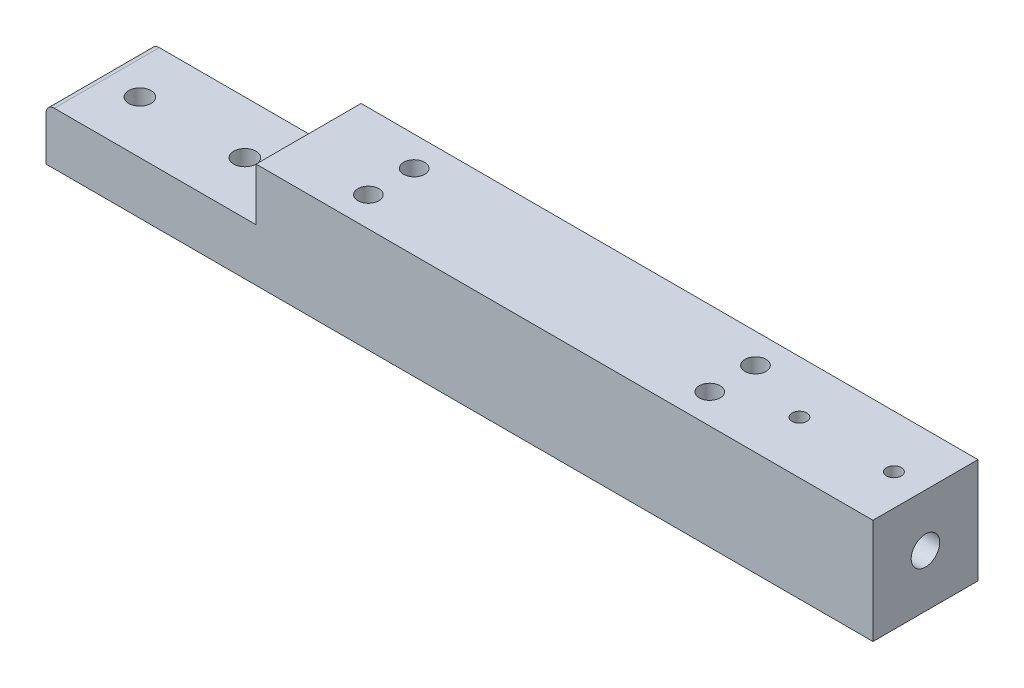
SolidWorks part; units mm, degrees
material "AISI 1020"
ref_plane "Front" through (0, 0, 0) normal (0, 0, 1) x (1, 0, 0)
ref_plane "Top" through (0, 0, 0) normal (0, 1, 0) x (1, 0, 0)
ref_plane "Right" through (0, 0, 0) normal (1, 0, 0) x (0, 0, -1)
sketch "Sketch1" plane through (0, 0, 0) normal (0, 0, 1) x (1, 0, 0)
  line L1 (0, 6.35) -> (100, 6.35)
  line L2 (0, 6.35) -> (0, -6.35)
  line L3 (0, -6.35) -> (100, -6.35)
  line L4 (100, 6.35) -> (100, -6.35)
  point P4 (0, 0)
  dimension "D1" = 12.7
  dimension "D2" = 100
extrude "Boss-Extrude1" add sketch "Sketch1" along normal mid plane 12.7
sketch "Sketch2" plane through (0, 0, 6.35) normal (0, 0, 1) x (1, 0, 0)
  line L1 (0, 6.35) -> (25.4, 6.35)
  line L2 (0, 6.35) -> (0, 0)
  line L3 (0, 0) -> (25.4, 0)
  line L4 (25.4, 6.35) -> (25.4, 0)
  dimension "D1" = 25.4
  dimension "D2" = 6.35
extrude "Cut-Extrude1" cut sketch "Sketch2" against normal through all
hole_wizard "#6-32 Tapped Hole1" positions "Sketch4" profile "Sketch5" tap size "#6-32" standard "Ansi Inch" end condition through all
sketch "Sketch4" plane through (0, 0, 0) normal (0, 1, 0) x (-1, 0, 0)
  line L0 (50, 0) -> (-50, 0) construction
  point P0 (-17.7, 0)
  point P1 (-5, 0)
sketch "Sketch5" plane through (17.7, 0, 0) normal (1, 0, 0) x (0, 0, 1)
  line L0 (0, 0) -> (0, 6.35)
  line L1 (0, 6.35) -> (1.3525, 6.35)
  line L2 (1.3525, 6.35) -> (1.3525, 0)
  line L5 (1.3525, 0) -> (0, 0)
  line L11 (0, -6.35) -> (0, 107.95) construction
  dimension "Thru Tap Drill Dia." = 2.7051
  dimension "Thru Tap Drill Depth" = 6.35
cosmetic thread "Hole Thread1" parameters "D2"=3.5052
cosmetic thread "Hole Thread2" parameters "D2"=3.5052
sketch "Sketch8" plane through (0, -6.35, 0) normal (0, 1, 0) x (1, 0, 0)
  line L0 (31.14, 4.0386) -> (66.14, 4.0386)
  line L1 (31.14, 1.4986) -> (66.14, 1.4986)
  line L2 (30.5743, 0) -> (90.4845, 0) construction
  line L3 (71.88, 12.488) -> (71.88, -9.4269) construction
  line L4 (100, -6.35) -> (100, 6.35) construction
  line L5 (25.4, 2.7686) -> (71.88, 2.7686) construction
  line L6 (25.4, 6.35) -> (25.4, -6.35) construction
  line L7 (31.14, 4.0386) -> (66.14, 1.4986) construction
  arc A0 (31.14, 1.4986) -> (31.14, 4.0386) centre (31.14, 2.7686) cw
  arc A1 (66.14, 1.4986) -> (66.14, 4.0386) centre (66.14, 2.7686) ccw
  point P17 (48.64, 2.7686)
  point P18 (48.64, 2.7686)
  dimension "D1" = 2.54
  dimension "D2" = 2.7686
  dimension "D3" = 35
  dimension "D4" = 28.12
hole_wizard "#8-32 Tapped Hole1" positions "Sketch10" profile "Sketch11" tap size "#8-32" standard "ANSI Inch"
sketch "Sketch10" plane through (100, 0, 0) normal (1, 0, 0) x (0, 0, -1)
  line L0 (-6.35, 6.35) -> (6.35, -6.35) construction
  point P0 (0, 0)
  point P9 (0, 0)
sketch "Sketch11" plane through (100, 0, 0) normal (0, 1, 0) x (0, 0, -1)
  line L0 (0, 0) -> (0, 11.0378)
  line L1 (0, 11.0378) -> (1.7272, 10)
  line L2 (1.7272, 10) -> (1.7272, 0)
  line L5 (1.7272, 0) -> (0, 0)
  line L10 (0, 11.0378) -> (-1.7272, 10) construction
  line L11 (0, -6.35) -> (0, 107.95) construction
  dimension "Tap Drill Dia." = 3.4544
  dimension "Tap Drill Depth" = 10
  dimension "Drill Angle" = 118
cosmetic thread "Hole Thread3" parameters "D1"=8.33, "D2"=4.1656
ref_axis "Axis1" through (31.14, -6.35, -2.7686) along (0, 1, 0)
hole_wizard "#2 (0.221) Diameter Hole1" positions "Sketch13" profile "Sketch14" hole size "#2" standard "ANSI Inch" end condition through all
sketch "Sketch13" plane through (0, 6.35, 0) normal (0, 1, 0) x (-1, 0, 0)
  line L0 (-35.4, -2.7686) -> (-76.675, 2.7686) construction
  line L3 (50, 0) -> (-50, 0) construction
  line L4 (-25.4, -6.35) -> (-25.4, 6.35) construction
  point P0 (-35.4, -2.7686)
  point P1 (-76.675, -2.7686)
  point P3 (-76.675, 2.7686)
  point P5 (-35.4, 2.7686)
  point P15 (-56.0375, 0)
  dimension "D1" = 41.275
  dimension "D2" = 5.5372
  dimension "D3" = 10
sketch "Sketch14" plane through (35.4, 6.35, -2.7686) normal (1, 0, 0) x (0, 0, 1)
  line L0 (0, 0) -> (0, 12.7)
  line L1 (0, 12.7) -> (1.27, 12.7)
  line L2 (1.27, 12.7) -> (1.27, 0)
  line L5 (1.27, 0) -> (0, 0)
  line L11 (0, -6.35) -> (0, 107.95) construction
  dimension "Thru Hole Dia." = 2.54
  dimension "Thru Hole Depth" = 12.7
sketch "Sketch15" plane through (0, 6.35, 0) normal (0, 1, 0) x (1, 0, 0)
  line L0 (100, -6.35) -> (100, 6.35) construction
  point P0 (96.19, 0)
  point P1 (84.76, 0)
  point P5 (100, 0)
  dimension "D1" = 3.81
  dimension "D2" = 15.24
hole_wizard "#2-56 Tapped Hole2" positions "Sketch18" profile "Sketch19" tap size "#2-56" standard "ANSI Inch"
sketch "Sketch18" plane through (0, 6.35, 0) normal (0, 1, 0) x (-1, 0, 0)
  point P0 (-84.76, 0)
  point P3 (-96.19, 0)
cosmetic thread "Hole Thread8" parameters "D1"=3.05, "D2"=2.1844
cosmetic thread "Hole Thread9" parameters "D1"=3.05, "D2"=2.1844
sketch "Sketch19" plane through (84.76, 6.35, 0) normal (1, 0, 0) x (0, 0, 1)
  line L0 (0, 0) -> (0, 5.5342)
  line L1 (0, 5.5342) -> (0.889, 5)
  line L2 (0.889, 5) -> (0.889, 0)
  line L5 (0.889, 0) -> (0, 0)
  line L10 (0, 5.5342) -> (-0.889, 5) construction
  line L11 (0, -6.35) -> (0, 107.95) construction
  dimension "Tap Drill Dia." = 1.778
  dimension "Tap Drill Depth" = 5
  dimension "Drill Angle" = 118
fillet "Fillet2" radius 1 1 edges at (0, 0, 0)
